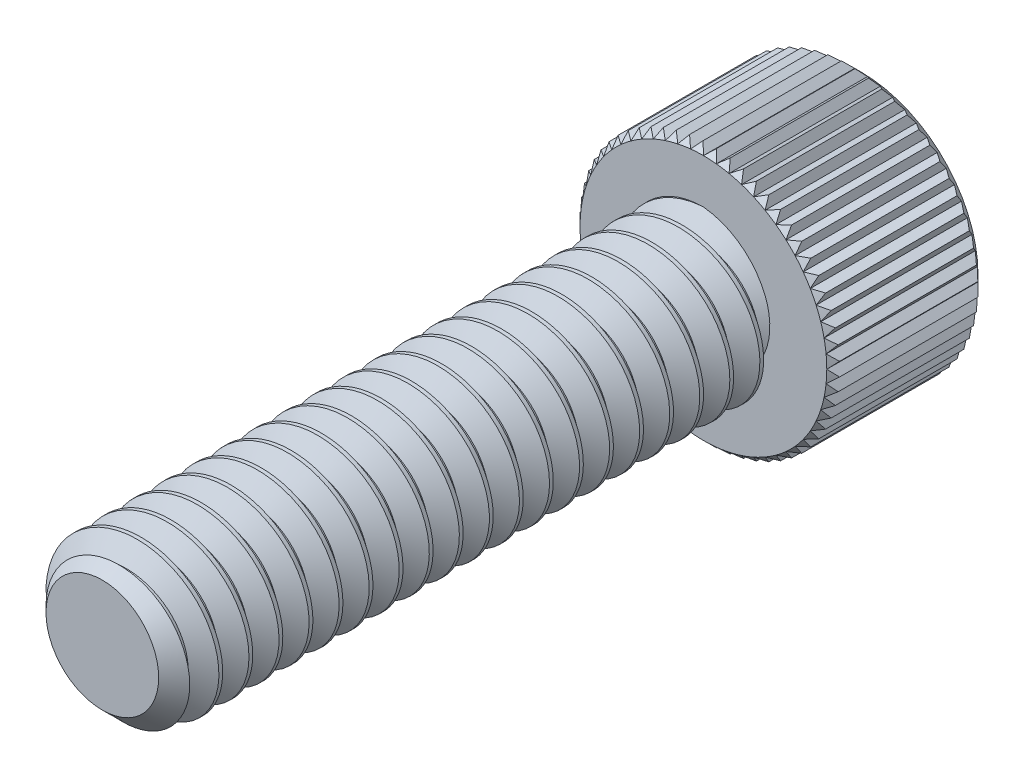
SolidWorks part; units mm, degrees
note: '?' marks a value the reader was unsure of.
ref_plane "Front Plane" through (0, 0, 0) normal (0, 0, 1) x (1, 0, 0)
ref_plane "Top Plane" through (0, 0, 0) normal (0, 1, 0) x (1, 0, 0)
ref_plane "Right Plane" through (0, 0, 0) normal (1, 0, 0) x (0, 0, -1)
sketch "Sketch0" plane through (0, 0, 0) normal (1, 0, 0) x (0, 0, -1)
  line L0 (0, 0) -> (15.875, 0) construction
  point P2 (20.0406, 0)
  point P4 (0, 0)
  dimension "D1" = 15.875
  dimension "D2" = 4.1656
  dimension "Min Thread" = 0
sketch "Sketch1" plane through (0, 0, 0) normal (0, 0, 1) x (1, 0, 0)
  circle A0 centre (0, 0) radius 2.0828
  dimension "OD" = 4.1656
extrude "Extrude1" add sketch "Sketch1" against normal blind 15.875
sketch "Sketch2" plane through (0, 0, 0) normal (0, 0, 1) x (1, 0, 0)
  circle A0 centre (0, 0) radius 2.0828 construction
  circle A1 centre (0, 0) radius 2.0828
curve "Helix/Spiral1" pitch 0.7937 height 16.6687 turns 21 parameters "pitch"=0.7937
chamfer "Chamfer3" distance 0.5953 angle 45 1 edges at (2.0828, 0, 0)
sketch "Sketch3" plane through (0, 0, 0) normal (1, 0, 0) x (0, 0, -1)
  line L0 (-0.6945, 2.0828) -> (-0.3969, 1.5672)
  line L1 (-0.3969, 1.5672) -> (-0.2977, 1.5672)
  line L2 (-0.2977, 1.5672) -> (0, 2.0828)
  line L3 (-0.6945, 2.0828) -> (0, 2.0828)
  line L4 (-0.3473, 2.0828) -> (-0.3473, 1.5672) construction
  line L5 (-0.5457, 1.825) -> (-0.1488, 1.825) construction
  line L6 (0, 2.0828) -> (0, -2.0828) construction
  dimension "D1" = 0.0992
  dimension "D2" = 0.3969
  dimension "D3" = 60
sweep "Cut-Sweep1" cut profiles "Sketch3" path "Helix/Spiral1"
sketch "Sketch5" plane through (0, 0, 0) normal (1, 0, 0) x (0, 0, -1)
  line L0 (15.875, -1.5805) -> (15.875, 1.4861) construction
  line L1 (15.875, 2.0828) -> (0, 2.0828)
  line L2 (15.875, 2.0828) -> (15.875, 0)
  line L3 (15.875, 0) -> (-0.7581, 0)
  line L4 (0, 0) -> (15.875, 0) construction
  line L5 (0, 2.0828) -> (-0.7581, 0)
  line L6 (0, 0) -> (18.415, 0) construction
  dimension "D1" = 70
  dimension "D3" = 2.54
revolve "partially thread" [suppressed] add sketch "Sketch5" angle 360 about L6
sketch "Sketch6" plane through (0, 0, -15.875) normal (0, 0, -1) x (-1, 0, 0)
  circle A0 centre (0, 0) radius 3.429
  dimension "head dia" = 6.858
extrude "Extrude2" add sketch "Sketch6" along normal blind 4.1656
sketch "Sketch7" plane through (0, 0, -20.0406) normal (0, 0, -1) x (-1, 0, 0)
  line L1 (0, 2.0622) -> (-1.7859, 1.0311)
  line L2 (-1.7859, 1.0311) -> (-1.7859, -1.0311)
  line L3 (-1.7859, -1.0311) -> (0, -2.0622)
  line L4 (0, -2.0622) -> (1.7859, -1.0311)
  line L5 (1.7859, -1.0311) -> (1.7859, 1.0311)
  line L6 (1.7859, 1.0311) -> (0, 2.0622)
  circle A0 centre (0, 0) radius 1.7859 construction
  dimension "hex dia" = 3.5719
extrude "Cut-Extrude1" cut sketch "Sketch7" against normal blind 2.6789
sketch "Sketch8" plane through (0, 0, -20.0406) normal (0, 0, -1) x (-1, 0, 0)
  circle A0 centre (0, 0) radius 2.0622
extrude "Cut-Extrude2" cut sketch "Sketch8" against normal through all draft 45
chamfer "Chamfer1" distance 0.3429 angle 45 1 edges at (-3.429, 0, -20.0406)
chamfer "Chamfer2" distance 0.1714 angle 45 1 edges at (-3.429, 0, -15.875)
sketch "Sketch9" plane through (0, 0, 0) normal (1, 0, 0) x (0, 0, -1)
  line L0 (0, 2.0828) -> (0, -2.0828) construction
  line L1 (1.9844, 2.0828) -> (1.9844, -2.0828) construction
  line L2 (20.0406, 3.429) -> (20.0406, -3.429) construction
  line L3 (15.875, 3.429) -> (15.875, -3.429) construction
  line L4 (15.875, 3.2576) -> (15.875, -3.2576) construction
  line L5 (20.0406, -3.0861) -> (20.0406, 3.0861) construction
  line L6 (15.875, -3.429) -> (15.875, 3.429) construction
  line L7 (0, 1.4875) -> (0, -1.4875) construction
  line L8 (-0.6945, 2.0828) -> (0, 2.0828) construction
  line L9 (1.9844, 0) -> (0, 0) construction
  dimension "D1" = 1.9844
sketch "Sketch10" plane through (0, 0, -15.875) normal (0, 0, 1) x (1, 0, 0)
  line L0 (-0.369, 3.6005) -> (0, 3.2576)
  line L1 (0, 3.2576) -> (0.369, 3.6005)
  line L2 (0, 3.2576) -> (0, 3.6005) construction
  line L3 (-0.369, 3.6005) -> (0.369, 3.6005)
  line L4 (0, -3.7667) -> (0, 3.7667) construction
  line L5 (0, 0) -> (0.1795, 3.4243) construction
  line L6 (-0.1795, 3.4243) -> (0, 0) construction
  circle A2 centre (0, 0) radius 3.429 construction
  circle A5 centre (0, 0) radius 3.2576 construction
  dimension "D1" = 6
  dimension "D2" = 0.3429
extrude "Cut-Extrude3" cut sketch "Sketch10" against normal through all
pattern_circular "CirPattern1" count 60 over 360 about axis through (0, 0, 0) along (0, 0, 1) of "Cut-Extrude3"
ref_plane "Contact Plane 1" through (0, 0, -15.875) normal (0, 0, 1) x (1, 0, 0)
ref_axis "Center Axis 1" through (0, 0, 0.8878) along (0, 0, -1)?
equation "\"D3@Helix/Spiral1\" = \"screw length@Extrude1\"+\"pitch@Helix/Spiral1\""
equation "\"D1@Sketch3\" = \"pitch@Helix/Spiral1\"*.125"
equation "\"D2@Sketch3\" = \"pitch@Helix/Spiral1\"*.5"
equation "\"D1@Cut-Extrude1\" = \"hex dia@Sketch7\"*.75"
equation "\"D1@Chamfer1\" = \"head dia@Sketch6\"*.05"
equation "\"D1@Sketch9\" = \"pitch@Helix/Spiral1\"*2.50"
equation "\"D1@Chamfer2\" = \"D1@Chamfer1\"/2"
equation "\"D1@Chamfer3\" = \"pitch@Helix/Spiral1\"*.750"
equation "\"D1@Sketch0\" = \"screw length@Extrude1\""
equation "\"D2@Sketch0\" = \"head depth@Extrude2\""
equation "\"D2@Sketch10\"=\"D1@Chamfer1\""
equation "\"D1@CirPattern1\"=\"D3@CirPattern1\"/\"D1@Sketch10\""
